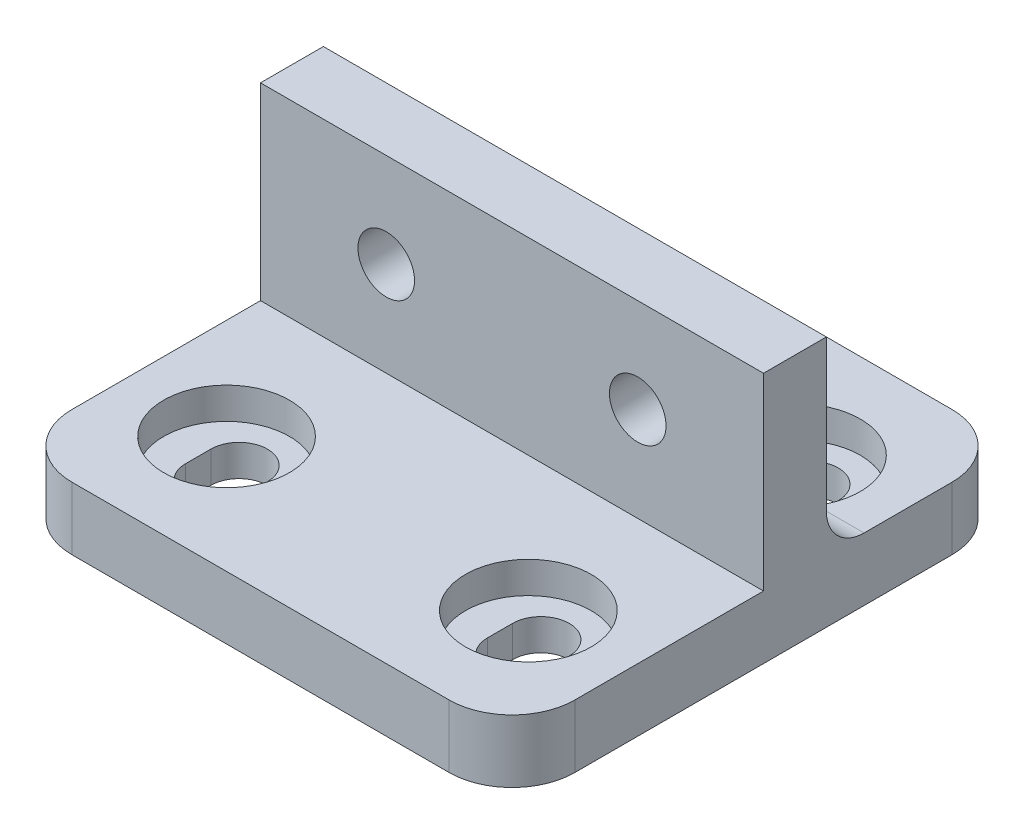
SolidWorks part; units mm, degrees
ref_plane "Front Plane" through (0, 0, 0) normal (0, 0, 1) x (1, 0, 0)
ref_plane "Top Plane" through (0, 0, 0) normal (0, 1, 0) x (1, 0, 0)
ref_plane "Right Plane" through (0, 0, 0) normal (1, 0, 0) x (0, 0, -1)
sketch "Sketch1" plane through (0, 0, 0) normal (0, 1, 0) x (1, 0, 0)
  line L1 (20, -20) -> (-20, -20)
  line L2 (20, -20) -> (20, 20)
  line L3 (20, 20) -> (-20, 20)
  line L4 (-20, -20) -> (-20, 20)
  line L5 (20, -20) -> (-20, 20) construction
  line L6 (20, 20) -> (-20, -20) construction
  point P0 (0, 0)
  dimension "D1" = 40
  dimension "D2" = 40
extrude "Boss-Extrude1" add sketch "Sketch1" along normal blind 5
sketch "Sketch2" plane through (0, 5, 0) normal (0, 1, 0) x (1, 0, 0)
  line L0 (-12, 9.7) -> (-12, 11.7) construction
  line L1 (-14.25, 9.7) -> (-14.25, 11.7)
  line L2 (-9.75, 9.7) -> (-9.75, 11.7)
  line L3 (0, -2.75) -> (0, 2.75) construction
  line L4 (12, 9.7) -> (12, 11.7) construction
  line L5 (14.25, 9.7) -> (14.25, 11.7)
  line L6 (9.75, 9.7) -> (9.75, 11.7)
  line L7 (-2.75, 0) -> (2.75, 0) construction
  line L8 (-12, -9.7) -> (-12, -11.7) construction
  line L9 (-14.25, -9.7) -> (-14.25, -11.7)
  line L10 (-9.75, -9.7) -> (-9.75, -11.7)
  line L11 (12, -9.7) -> (12, -11.7) construction
  line L12 (14.25, -9.7) -> (14.25, -11.7)
  line L13 (9.75, -9.7) -> (9.75, -11.7)
  arc A0 (-14.25, 9.7) -> (-9.75, 9.7) centre (-12, 9.7) ccw
  arc A1 (-9.75, 11.7) -> (-14.25, 11.7) centre (-12, 11.7) ccw
  arc A2 (14.25, 9.7) -> (9.75, 9.7) centre (12, 9.7) cw
  arc A3 (9.75, 11.7) -> (14.25, 11.7) centre (12, 11.7) cw
  arc A4 (-14.25, -9.7) -> (-9.75, -9.7) centre (-12, -9.7) cw
  arc A5 (-9.75, -11.7) -> (-14.25, -11.7) centre (-12, -11.7) cw
  arc A6 (14.25, -9.7) -> (9.75, -9.7) centre (12, -9.7) ccw
  arc A7 (9.75, -11.7) -> (14.25, -11.7) centre (12, -11.7) ccw
  point P2 (-12, 10.7)
  point P12 (12, 10.7)
  point P21 (-12, -10.7)
  point P28 (12, -10.7)
  dimension "D1" = 2.25
  dimension "D2" = 2
  dimension "D3" = 12
  dimension "D4" = 10.7
extrude "Cut-Extrude1" cut sketch "Sketch2" against normal blind 5
fillet "Fillet1" radius 5 4 edges at (20, 2.5, 20) (-20, 2.5, 20) (-20, 2.5, -20) (20, 2.5, -20)
sketch "Sketch3" plane through (0, 5, 0) normal (0, 1, 0) x (1, 0, 0)
  line L0 (-20, 15) -> (-20, -15) construction
  line L1 (20, 0) -> (-20, 0)
  line L2 (20, 0) -> (20, 5)
  line L3 (20, 5) -> (-20, 5)
  line L4 (-20, 0) -> (-20, 5)
  line L5 (20, 0) -> (-20, 5) construction
  line L6 (20, 5) -> (-20, 0) construction
  point P0 (0, 2.5)
  dimension "D1" = 5
  dimension "D2" = 0
extrude "Boss-Extrude2" add sketch "Sketch3" along normal blind 15
sketch "Sketch6" plane through (0, 5, 0) normal (0, 1, 0) x (1, 0, 0)
  circle A0 centre (-12, -10.7) radius 5
extrude "Cut-Extrude2" cut sketch "Sketch6" against normal blind 2.5
mirror "Mirror1" about plane through (0, 0, 0) normal (1, 0, 0) of "Cut-Extrude2"
mirror "Mirror2" about plane through (0, 0, 0) normal (0, 0, 1) of "Mirror1"
sketch "Sketch7" plane through (0, 0, -5) normal (0, 0, -1) x (-1, 0, 0)
  line L0 (-20, 20) -> (-20, 5) construction
  line L1 (20, 20) -> (20, 5) construction
  circle A0 centre (-10, 12.5) radius 2.25
  circle A1 centre (10, 12.5) radius 2.25
  dimension "D1" = 10
  dimension "D2" = 10
extrude "Cut-Extrude3" cut sketch "Sketch7" against normal blind 10.5
fillet "Fillet2" radius 3 1 edges at (0, 5, -5)
